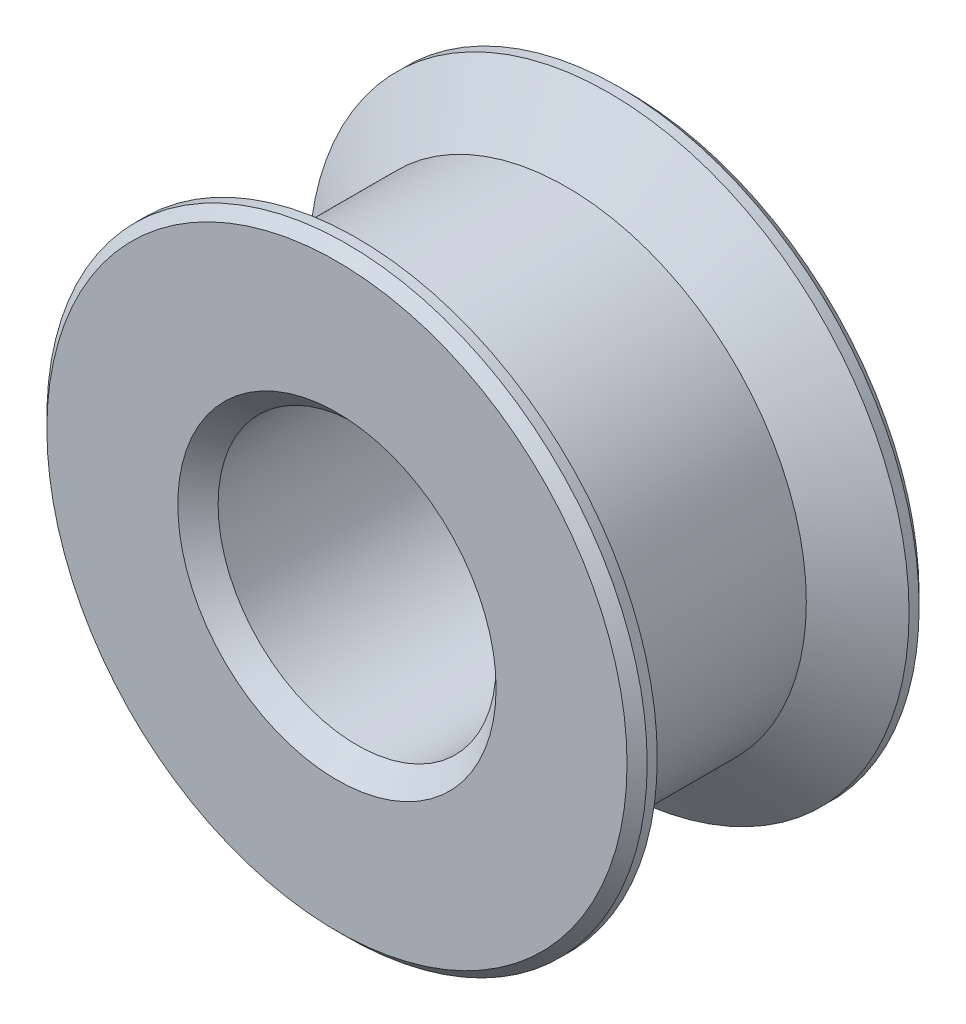
SolidWorks part; units mm, degrees
material "PLA"
ref_plane "Front Plane" through (0, 0, 0) normal (0, 0, 1) x (1, 0, 0)
ref_plane "Top Plane" through (0, 0, 0) normal (0, 1, 0) x (1, 0, 0)
ref_plane "Right Plane" through (0, 0, 0) normal (1, 0, 0) x (0, 0, -1)
sketch "Sketch1" plane through (0, 0, 0) normal (0, 0, 1) x (1, 0, 0)
  circle A0 centre (0, 0) radius 6.9
  circle A1 centre (0, 0) radius 11.9
  dimension "D1" = 13.8
  dimension "D2" = 5
extrude "Boss-Extrude1" add sketch "Sketch1" along normal mid plane 12.5
sketch "Sketch2" plane through (0, 0, 6.25) normal (0, 0, 1) x (1, 0, 0)
  circle A5 centre (0, 0) radius 6.9 construction
  circle A6 centre (0, 0) radius 6.9
  circle A8 centre (0, 0) radius 14.9
  circle A9 centre (0, 0) radius 14.9
  dimension "D1" = 3
extrude "Boss-Extrude2" add sketch "Sketch2" along normal blind 1
mirror "Mirror1" about plane through (0, 0, 0) normal (0, 0, 1) of "Boss-Extrude2"
chamfer "Chamfer1" distance 3 angle 35 2 edges at (11.9, 0, 6.25) (11.9, 0, -6.25) first distance on face at (11.9, 0, 6.25) first distance on face at (11.9, 0, -6.25)
chamfer "Chamfer2" distance 0.5 angle 45 2 edges at (14.9, 0, 7.25) (14.9, 0, -7.25)
chamfer "Chamfer3" distance 1 angle 45 2 edges at (6.9, 0, -7.25) (6.9, 0, 7.25)
